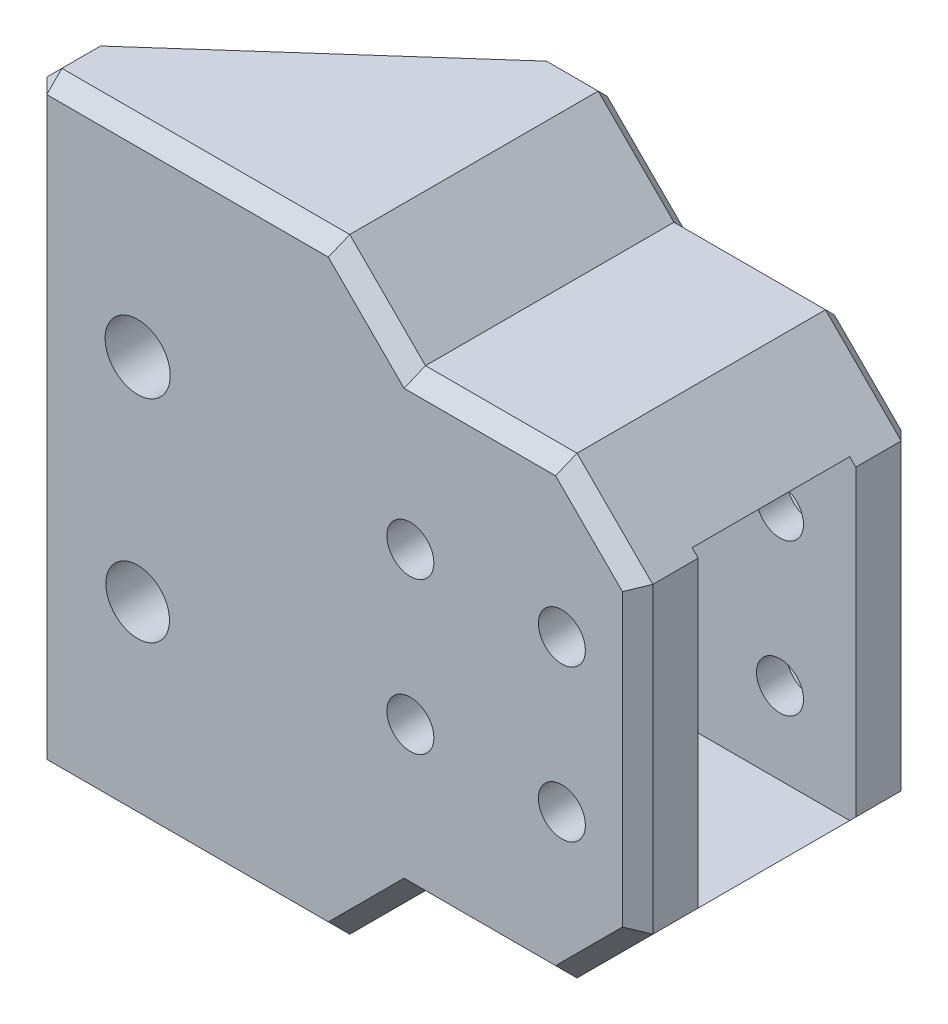
SolidWorks part; units mm, degrees
material "ABS"
ref_plane "前视基准面" through (0, 0, 0) normal (0, 0, 1) x (1, 0, 0)
ref_plane "上视基准面" through (0, 0, 0) normal (0, 1, 0) x (1, 0, 0)
ref_plane "右视基准面" through (0, 0, 0) normal (1, 0, 0) x (0, 0, -1)
other "Configuration Table"
sketch "草图1" plane through (0, 0, 0) normal (0, 0, 1) x (1, 0, 0)
  line L0 (0, 15) -> (40, 15) construction
  line L1 (0, 0) -> (40, 0)
  line L2 (0, 0) -> (0, 30)
  line L3 (0, 30) -> (40, 30)
  line L4 (40, 0) -> (40, 30)
  circle A0 centre (7, 22) radius 2.15
  circle A1 centre (7, 8) radius 2.1
  circle A2 centre (35, 20) radius 1.55
  circle A3 centre (25, 20) radius 1.55
  circle A4 centre (25, 10) radius 1.55
  circle A5 centre (35, 10) radius 1.55
  point P9 (0, 15)
  dimension "D5" = 4.3
  dimension "D6" = 4.2
  dimension "D9" = 3.1
  dimension "D1" = 30
  dimension "D2" = 40
  dimension "D3" = 7
  dimension "D4" = 7
  dimension "D7" = 7
  dimension "D8" = 7
  dimension "D10" = 5
  dimension "D11" = 5
  dimension "D12" = 2
  dimension "D13" = 2
extrude "凸台-拉伸1" add sketch "草图1" along normal blind 4
chamfer "倒角1" distance 5 angle 45 2 edges at (40, 0, 2) (40, 30, 2)
sketch "草图3" plane through (0, 0, 0) normal (0, 0, -1) x (-1, 0, 0)
  line L0 (-40, 5) -> (-40, 25) construction
  line L1 (-40, 25) -> (-20, 25)
  line L3 (-40, 5) -> (-20, 5)
  line L4 (-20, 25) -> (-20, 5)
  line L5 (-40, 25) -> (-35, 30)
  line L6 (-35, 30) -> (-16.2, 30)
  line L7 (-35, 30) -> (0, 30) construction
  line L8 (-16.2, 30) -> (-16.2, 0)
  line L9 (0, 0) -> (-35, 0) construction
  line L10 (-16.2, 0) -> (-35, 0)
  line L11 (-35, 0) -> (-40, 5)
  line L12 (0, 30) -> (0, 0) construction
  circle A0 centre (-25, 20) radius 1.55 construction
  circle A1 centre (-25, 10) radius 1.55 construction
  dimension "D1" = 5
  dimension "D2" = 5
  dimension "D3" = 5
  dimension "D4" = 16.2
extrude "凸台-拉伸2" add sketch "草图3" along normal blind 10.4
sketch "草图4" plane through (0, 0, -10.4) normal (0, 0, -1) x (-1, 0, 0)
  line L0 (-40, 25) -> (-40, 5)
  line L1 (-40, 5) -> (-35, 0)
  line L2 (-35, 0) -> (-16.2, 0)
  line L3 (-16.2, 0) -> (-16.2, 30)
  line L4 (-16.2, 30) -> (-35, 30)
  line L5 (-35, 30) -> (-40, 25)
  circle A0 centre (-35, 20) radius 1.55
  circle A1 centre (-25, 20) radius 1.55
  circle A2 centre (-25, 10) radius 1.55
  circle A3 centre (-35, 10) radius 1.55
extrude "凸台-拉伸3" add sketch "草图4" along normal blind 4
chamfer "倒角2" [suppressed] distance 5 angle 45
sketch "草图7" plane through (0, 0, 0) normal (0, -1, 0) x (1, 0, 0)
  line L0 (0, 0) -> (16.2, -14.4)
  line L1 (16.2, -14.4) -> (30, -14.4)
  line L2 (35, -14.4) -> (16.2, -14.4) construction
  line L3 (30, -14.4) -> (30, 4)
  line L4 (0, 4) -> (35, 4) construction
  line L5 (30, 4) -> (0, 4)
  line L6 (0, 4) -> (0, 0)
  line L7 (35, -14.4) -> (35, 4) construction
  dimension "D1" = 5
extrude "凸台-拉伸4" add sketch "草图7" along normal blind 5
sketch "草图8" plane through (0, 30, 0) normal (0, 1, 0) x (1, 0, 0)
  line L0 (0, 0) -> (16.2, 14.4)
  line L1 (16.2, 14.4) -> (30, 14.4)
  line L2 (30, 14.4) -> (30, -4)
  line L3 (35, -4) -> (0, -4) construction
  line L4 (30, -4) -> (0, -4)
  line L5 (0, -4) -> (0, 0)
  line L6 (35, -4) -> (35, 14.4) construction
  dimension "D1" = 5
extrude "凸台-拉伸5" add sketch "草图8" along normal blind 5
chamfer "倒角3" distance 10 angle 45 2 edges at (30, 35, -5.2) (30, -5, -5.2)
chamfer "倒角4" distance 1 angle 45 25 edges at (8.1, 30, -7.2) (8.1, 0, -7.2) (22.5, 32.5, 4) (10, 35, 4) (0, 15, 4) (0, 35, 2) (30, 30, 4) (37.5, 27.5, 4) (40, 15, 4) (37.5, 2.5, 4) (30, 0, 4) (22.5, -2.5, 4) (10, -5, 4) (0, -5, 2) (8.1, 35, -7.2) (8.1, -5, -7.2) (18.1, 35, -14.4) (22.5, 32.5, -14.4) (30, 30, -14.4) (37.5, 27.5, -14.4) (40, 15, -14.4) (18.1, -5, -14.4) (22.5, -2.5, -14.4) (30, 0, -14.4) (37.5, 2.5, -14.4)
sketch "草图9" plane through (0, 0, -14.4) normal (0, 0, -1) x (-1, 0, 0)
  line L1 (-35, 16.7668) -> (-32.2, 18.3834)
  line L2 (-32.2, 18.3834) -> (-32.2, 21.6166)
  line L3 (-32.2, 21.6166) -> (-35, 23.2332)
  line L4 (-35, 23.2332) -> (-37.8, 21.6166)
  line L5 (-37.8, 21.6166) -> (-37.8, 18.3834)
  line L6 (-37.8, 18.3834) -> (-35, 16.7668)
  line L12 (26.2459, 18.7199) -> (29.0459, 20.3364)
  line L13 (29.0459, 20.3364) -> (29.0459, 23.5696)
  line L14 (29.0459, 23.5696) -> (26.2459, 25.1862)
  line L15 (26.2459, 25.1862) -> (23.4459, 23.5696)
  line L16 (23.4459, 23.5696) -> (23.4459, 20.3364)
  line L17 (23.4459, 20.3364) -> (26.2459, 18.7199)
  line L25 (-35, 6.7668) -> (-32.2, 8.3834)
  line L26 (-32.2, 8.3834) -> (-32.2, 11.6166)
  line L27 (-32.2, 11.6166) -> (-35, 13.2332)
  line L28 (-35, 13.2332) -> (-37.8, 11.6166)
  line L29 (-37.8, 11.6166) -> (-37.8, 8.3834)
  line L30 (-37.8, 8.3834) -> (-35, 6.7668)
  line L31 (-25, 6.7668) -> (-22.2, 8.3834)
  line L32 (-22.2, 8.3834) -> (-22.2, 11.6166)
  line L33 (-22.2, 11.6166) -> (-25, 13.2332)
  line L34 (-25, 13.2332) -> (-27.8, 11.6166)
  line L35 (-27.8, 11.6166) -> (-27.8, 8.3834)
  line L36 (-27.8, 8.3834) -> (-25, 6.7668)
  line L37 (-25, 16.7668) -> (-22.2, 18.3834)
  line L38 (-22.2, 18.3834) -> (-22.2, 21.6166)
  line L39 (-22.2, 21.6166) -> (-25, 23.2332)
  line L40 (-25, 23.2332) -> (-27.8, 21.6166)
  line L41 (-27.8, 21.6166) -> (-27.8, 18.3834)
  line L42 (-27.8, 18.3834) -> (-25, 16.7668)
  circle A0 centre (-35, 20) radius 2.8 construction
  circle A2 centre (26.2459, 21.953) radius 2.8 construction
  circle A4 centre (-35, 10) radius 2.8 construction
  circle A5 centre (-25, 10) radius 2.8 construction
  circle A6 centre (-25, 20) radius 2.8 construction
  dimension "D1" = 5.6
  dimension "D2" = 5.6
  dimension "D3" = 5.6
  dimension "D4" = 5.6
extrude "切除-拉伸1" cut sketch "草图9" against normal blind 2
sketch "草图10" plane through (20, 0, 0) normal (1, 0, 0) x (0, 0, -1)
  line L0 (0, 25) -> (0, 5) construction
  line L6 (0, 25.4) -> (10.4, 25.4)
  line L7 (0, 25.4) -> (0, 4.6)
  line L9 (0, 4.6) -> (10.4, 4.6)
  line L10 (10.4, 25.4) -> (10.4, 4.6)
  line L11 (10.4, 25) -> (10.4, 5) construction
  line L12 (10.4, 25) -> (0, 25) construction
  line L13 (10.4, 5) -> (0, 5) construction
  dimension "D1" = 0.4
  dimension "D2" = 0.4
extrude "切除-拉伸2" cut sketch "草图10" along normal through all
